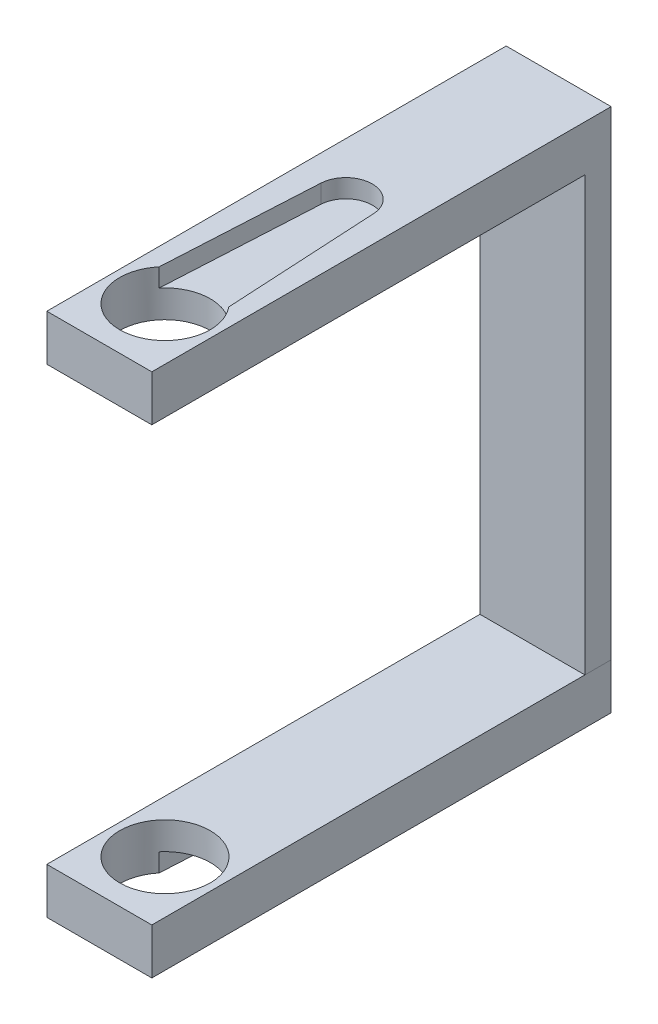
SolidWorks part; units mm, degrees
note: The reader was unsure of these and kept them because the rebuilt part matched: shared geometry of "Sketch2<3>".
ref_plane "Front Plane" through (0, 0, 0) normal (0, 0, 1) x (1, 0, 0)
ref_plane "Top Plane" through (0, 0, 0) normal (0, 1, 0) x (1, 0, 0)
ref_plane "Right Plane" through (0, 0, 0) normal (1, 0, 0) x (0, 0, -1)
sketch "Sketch2" plane through (0, 0, 0) normal (0, 0, 1) x (1, 0, 0)
  line L1 (-8.6815, 4.8865) -> (-0.6815, 4.8865)
  line L2 (-8.6815, 4.8865) -> (-8.6815, -35.1135)
  line L3 (-8.6815, -35.1135) -> (-0.6815, -35.1135)
  line L4 (-0.6815, 4.8865) -> (-0.6815, -35.1135)
  line L13 (-8.6815, 4.8865) -> (-0.6815, 4.8865)
  line L14 (-8.6815, 4.8865) -> (-8.6815, 1.3865)
  line L15 (-8.6815, 1.3865) -> (-0.6815, 1.3865)
  line L16 (-0.6815, 4.8865) -> (-0.6815, 1.3865)
  line L21 (-8.6815, -35.1135) -> (-0.6815, -35.1135)
  line L22 (-8.6815, -35.1135) -> (-8.6815, -31.6135)
  line L23 (-8.6815, -31.6135) -> (-0.6815, -31.6135)
  line L24 (-0.6815, -35.1135) -> (-0.6815, -31.6135)
  dimension "D1" = 8
  dimension "D2" = 40
  dimension "D3" = 3.5
  dimension "D4" = 3.5
extrude "Boss-Extrude2" add sketch "Sketch2" along normal blind 35 contours L2 L15 L4 L1 | L22 L21 L24 L23
extrude "Boss-Extrude3" add sketch "Sketch2<3>" along normal blind 2 contours L15 L2 L3 L4
sketch "Sketch2<3>" plane through (0, 0, 0) normal (0, 0, 1) x (1, 0, 0) same geometry as "Sketch2"
sketch "Sketch3" plane through (0, 4.8865, 0) normal (0, 1, 0) x (1, 0, 0)
  line L1 (-4.2779, 20.7062) -> (-18.3279, 20.7062) construction
  line L3 (-2.67, -16.1058) -> (-2.0315, -27.7909)
  line L4 (-7.3315, -27.7909) -> (-6.693, -16.1058)
  line L5 (-4.6815, -30) -> (-4.6815, -35) construction
  line L6 (-8.6815, -35) -> (-0.6815, -35) construction
  arc A1 (-7.3315, -27.7909) -> (-2.0315, -27.7909) centre (-4.6815, -30) ccw
  arc A2 (-2.67, -16.1058) -> (-6.693, -16.1058) centre (-4.6815, -16.2157) ccw
  dimension "D1" = 5.3
  dimension "D2" = 5
extrude "Cut-Extrude2" cut sketch "Sketch3" against normal blind 1.4
sketch "Sketch5" plane through (0, 3.4865, 0) normal (0, 1, 0) x (1, 0, 0)
  circle A0 centre (-4.6815, -30) radius 3.45
extrude "Cut-Extrude3" cut sketch "Sketch5" against normal up to next (2.1 mm away)
sketch "Sketch6" plane through (0, -35.1135, 0) normal (0, -1, 0) x (1, 0, 0)
  line L0 (-6.693, 16.1058) -> (-7.3315, 27.7909)
  line L1 (-2.0315, 27.7909) -> (-2.67, 16.1058)
  line L2 (-4.6815, 30) -> (-4.6815, 35) construction
  line L3 (-8.6815, 35) -> (-0.6815, 35) construction
  arc A0 (-2.0315, 27.7909) -> (-7.3315, 27.7909) centre (-4.6815, 30) ccw
  arc A1 (-6.693, 16.1058) -> (-2.67, 16.1058) centre (-4.6815, 16.2157) ccw
  dimension "D1" = 5
extrude "Cut-Extrude4" cut sketch "Sketch6" against normal blind 1.4
sketch "Sketch7" plane through (0, -35.1135, 0) normal (0, -1, 0) x (1, 0, 0)
  circle A0 centre (-4.6815, 30) radius 3.45
extrude "Cut-Extrude5" cut sketch "Sketch7" against normal up to next
